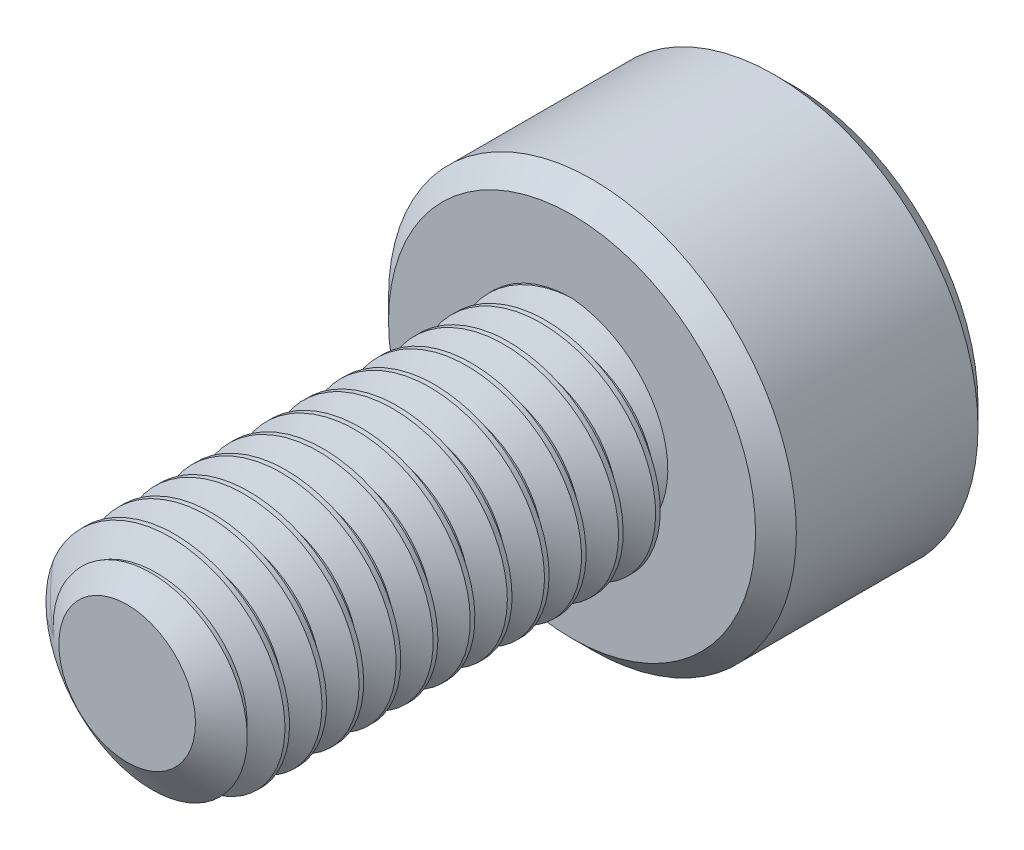
SolidWorks part; units mm, degrees
ref_plane "Front Plane" through (0, 0, 0) normal (0, 0, 1) x (1, 0, 0)
ref_plane "Top Plane" through (0, 0, 0) normal (0, 1, 0) x (1, 0, 0)
ref_plane "Right Plane" through (0, 0, 0) normal (1, 0, 0) x (0, 0, -1)
sketch "Sketch1" plane through (0, 0, 0) normal (0, 0, 1) x (1, 0, 0)
  circle A0 centre (0, 0) radius 1.5
  dimension "OD" = 3
extrude "Extrude1" add sketch "Sketch1" against normal blind 6
sketch "Sketch2" plane through (0, 0, 0) normal (0, 0, 1) x (1, 0, 0)
  circle A0 centre (0, 0) radius 1.5 construction
  circle A1 centre (0, 0) radius 1.5
curve "Helix/Spiral1" pitch 0.5 height 6.5 radius 1.5 centre (0, 0, 0) axis (0, 0, -1) start towards (0, 1, 0) parameters "pitch"=0.5
sketch "Sketch3" plane through (0, 0, 0) normal (1, 0, 0) x (0, 0, -1)
  line L0 (-0.4375, 1.5) -> (-0.25, 1.1752)
  line L1 (-0.25, 1.1752) -> (-0.1875, 1.1752)
  line L2 (-0.1875, 1.1752) -> (0, 1.5)
  line L3 (-0.4375, 1.5) -> (0, 1.5)
  line L4 (-0.2188, 1.5) -> (-0.2188, 1.1752) construction
  line L5 (-0.3438, 1.3376) -> (-0.0938, 1.3376) construction
  line L6 (0, 1.5) -> (0, -1.5) construction
  dimension "D1" = 0.0625
  dimension "D2" = 0.25
  dimension "D3" = 60
sweep "Cut-Sweep1" cut profiles "Sketch3" path "Helix/Spiral1"
sketch "Sketch4" plane through (0, 0, 0) normal (1, 0, 0) x (0, 0, -1)
  line L0 (0.4053, 1.5) -> (0, 0.9212)
  line L1 (0, 0.9212) -> (0, 1.5)
  line L2 (0.4053, 1.5) -> (0, 1.5)
  line L3 (-0.4375, 1.5) -> (0, 1.5) construction
  line L4 (0, 0) -> (7.0209, 0) construction
  dimension "D1" = 55
  dimension "D2" = 0.254
revolve "Cut-Revolve1" cut sketch "Sketch4" angle 360 about L4
sketch "Sketch6" plane through (0, 0, -6) normal (0, 0, -1) x (-1, 0, 0)
  circle A0 centre (0, 0) radius 2.75
  dimension "head dia" = 5.5
extrude "Extrude2" add sketch "Sketch6" along normal blind 3
sketch "Sketch7" plane through (0, 0, -9) normal (0, 0, -1) x (-1, 0, 0)
  line L1 (0, 1.4434) -> (-1.25, 0.7217)
  line L2 (-1.25, 0.7217) -> (-1.25, -0.7217)
  line L3 (-1.25, -0.7217) -> (0, -1.4434)
  line L4 (0, -1.4434) -> (1.25, -0.7217)
  line L5 (1.25, -0.7217) -> (1.25, 0.7217)
  line L6 (1.25, 0.7217) -> (0, 1.4434)
  circle A0 centre (0, 0) radius 1.25 construction
  dimension "hex dia" = 2.5
extrude "Cut-Extrude1" cut sketch "Sketch7" against normal blind 1.875
sketch "Sketch8" plane through (0, 0, -9) normal (0, 0, -1) x (-1, 0, 0)
  circle A0 centre (0, 0) radius 1.4434
extrude "Cut-Extrude2" cut sketch "Sketch8" against normal through all draft 45
chamfer "Chamfer1" distance 0.275 angle 45 2 edges at (-2.75, 0, -9) (-2.75, 0, -6)
sketch "Sketch10" plane through (0, 0, -6) normal (0, 0, 1) x (1, 0, 0)
  circle A1 centre (0, 0) radius 1.5
  circle A2 centre (0, 0) radius 1.5
  dimension "D1" = 0
ref_plane "Plane1" through (0, 0, 0) normal (0, 0, 1) x (1, 0, 0)
extrude "partial thread" [suppressed] add sketch "Sketch10" along normal up to surface (36 mm away) separate body up to plane "Plane1"
chamfer "Chamfer2" [suppressed] distance 0.06 angle 45
combine bodies "Combine1" [suppressed] operation type add bodies to combine 107 108
sketch "Sketch9" plane through (0, 0, 0) normal (1, 0, 0) x (0, 0, -1)
  line L0 (0, 1.5) -> (0, -1.5) construction
  line L1 (1.25, 1.5) -> (1.25, -1.5) construction
  dimension "D1" = 1.25
equation "\"D3@Helix/Spiral1\" = \"screw length@Extrude1\"+\"pitch@Helix/Spiral1\""
equation "\"D1@Sketch3\" = \"pitch@Helix/Spiral1\"*.125"
equation "\"D2@Sketch3\" = \"pitch@Helix/Spiral1\"*.5"
equation "\"D1@Cut-Extrude1\" = \"hex dia@Sketch7\"*.75"
equation "\"D1@Chamfer1\" = \"head dia@Sketch6\"*.05"
equation "\"D1@Sketch9\" = \"pitch@Helix/Spiral1\"*2.5"
equation "\"D1@Chamfer2\"=\"OD@Sketch1\"*.02"
